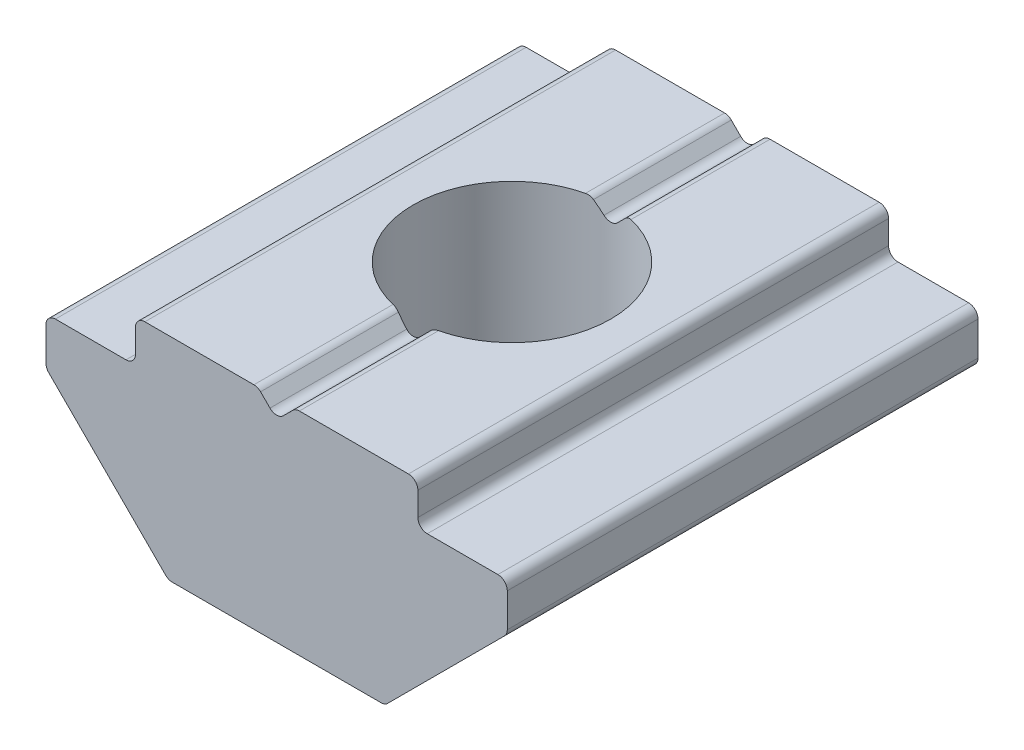
SolidWorks part; units mm, degrees
ref_plane "Front Plane" through (0, 0, 0) normal (0, 0, 1) x (1, 0, 0)
ref_plane "Top Plane" through (0, 0, 0) normal (0, 1, 0) x (1, 0, 0)
ref_plane "Right Plane" through (0, 0, 0) normal (1, 0, 0) x (0, 0, -1)
ref_plane "Plane1" through (0, 0, 5) normal (0, 0, 1) x (1, 0, 0)
sketch "Sketch1" plane through (0, 0, 5) normal (0, 0, 1) x (1, 0, 0)
  line L0 (4.9, -1) -> (4.9, 0.9)
  line L1 (4.9, 0.9) -> (-4.9, 0.9)
  line L2 (-4.9, 0.9) -> (-4.9, -1)
  line L3 (-4.9, -1) -> (-2.3, -3.6)
  line L4 (-2.3, -3.6) -> (2.3, -3.6)
  line L5 (2.3, -3.6) -> (4.9, -1)
extrude "Boss-Extrude1" add sketch "Sketch1" against normal blind 10
sketch "Sketch2" plane through (0, 0, -5) normal (0, 0, -1) x (-1, 0, 0)
  line L0 (4.9, 0.9) -> (3, 0.9)
  line L1 (3, 0.9) -> (3, 0)
  line L2 (3, 0) -> (4.9, 0)
  line L3 (4.9, 0) -> (4.9, 0.9)
extrude "Cut-Extrude1" cut sketch "Sketch2" against normal through all
sketch "Sketch3" plane through (0, 0, -5) normal (0, 0, -1) x (-1, 0, 0)
  line L0 (-4.9, 0) -> (-3, 0)
  line L1 (-3, 0) -> (-3, 0.9)
  line L2 (-3, 0.9) -> (-4.9, 0.9)
  line L3 (-4.9, 0.9) -> (-4.9, 0)
extrude "Cut-Extrude2" cut sketch "Sketch3" against normal through all
sketch "Sketch4" plane through (0, 0, -5) normal (0, 0, -1) x (-1, 0, 0)
  line L0 (0.4, 0.9) -> (-0.4, 0.9)
  line L1 (-0.4, 0.9) -> (0, 0.5)
  line L2 (0, 0.5) -> (0.4, 0.9)
extrude "Cut-Extrude3" cut sketch "Sketch4" against normal through all
hole_wizard "Ø4.2 (4.2) Diameter Hole1" positions "Sketch6" profile "Sketch5" hole size "Ø4.2" standard "ANSI Metric"
sketch "Sketch6" plane through (0, -3.6, 0) normal (0, -1, 0) x (-1, 0, 0)
  point P0 (0, 0)
sketch "Sketch5" plane through (0, -3.6, 0) normal (1, 0, 0) x (0, 0, -1)
  line L0 (0, 0) -> (0, 4.5)
  line L1 (0, 4.5) -> (2.1, 4.5)
  line L2 (2.1, 4.5) -> (2.1, 0)
  line L5 (2.1, 0) -> (0, 0)
  line L11 (0, -6.35) -> (0, 107.95) construction
  dimension "Thru Hole Dia." = 4.2
  dimension "Thru Hole Depth" = 4.5
fillet "Fillet1" radius 0.2 16 edges at (4.9, 0, 0) (3, 0, 0) (-4.9, -1, 0) (3, 0.9, 0) (-3, 0, 0) (0.4, 0.9, -3.5308) (0, 0.5, 3.55) (-0.4, 0.9, -3.5308) (4.9, -1, 0) (-3, 0.9, 0) (0, 0.5, -3.55) (-0.4, 0.9, 3.5308) (-4.9, 0, 0) (-2.3, -3.6, 0) (0.4, 0.9, 3.5308) (2.3, -3.6, 0) tangent propagation no
